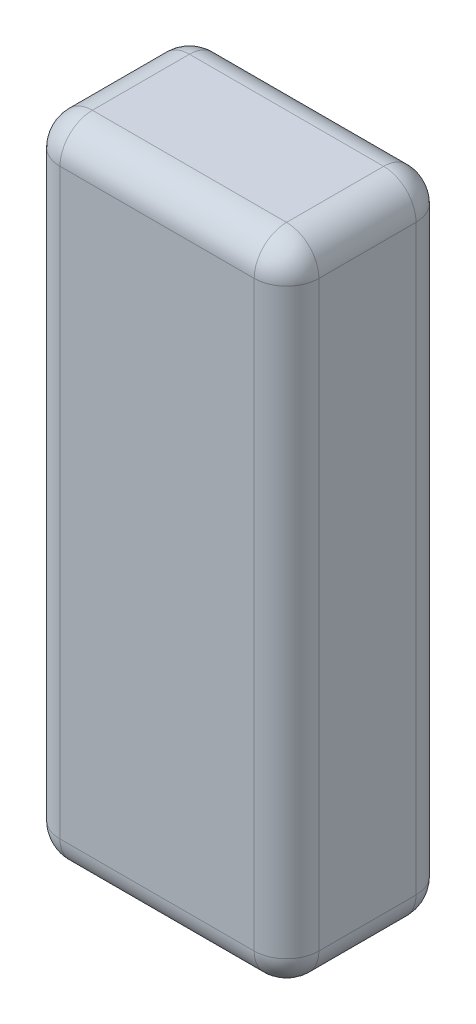
SolidWorks part; units mm, degrees
ref_plane "Front Plane" through (0, 0, 0) normal (0, 0, 1) x (1, 0, 0)
ref_plane "Top Plane" through (0, 0, 0) normal (0, 1, 0) x (1, 0, 0)
ref_plane "Right Plane" through (0, 0, 0) normal (1, 0, 0) x (0, 0, -1)
sketch "Sketch1" plane through (0, 0, 0) normal (0, 0, 1) x (1, 0, 0)
  line L1 (10, 0) -> (70, 0)
  line L2 (0, 10) -> (0, 190)
  line L3 (10, 200) -> (70, 200)
  line L4 (80, 10) -> (80, 190)
  arc A0 (70, 0) -> (80, 10) centre (70, 10) ccw
  arc A1 (10, 0) -> (0, 10) centre (10, 10) cw
  arc A2 (70, 200) -> (80, 190) centre (70, 190) cw
  arc A3 (0, 190) -> (10, 200) centre (10, 190) cw
  point P9 (0, 0)
  dimension "D1" = 10
extrude "Boss-Extrude1" add sketch "Sketch1" along normal blind 50 contours L2 A3 L3 A2 L4 A0 L1 A1
fillet "Fillet1" radius 10 16 edges at (77.0711, 2.9289, 50) (40, 0, 50) (2.9289, 2.9289, 50) (0, 100, 50) (2.9289, 197.0711, 50) (40, 200, 50) (77.0711, 197.0711, 50) (77.0711, 2.9289, 0) (40, 0, 0) (2.9289, 2.9289, 0) (0, 100, 0) (2.9289, 197.0711, 0) (40, 200, 0) (77.0711, 197.0711, 0) (80, 100, 50) (80, 100, 0)
shell "Shell3" thickness 5
